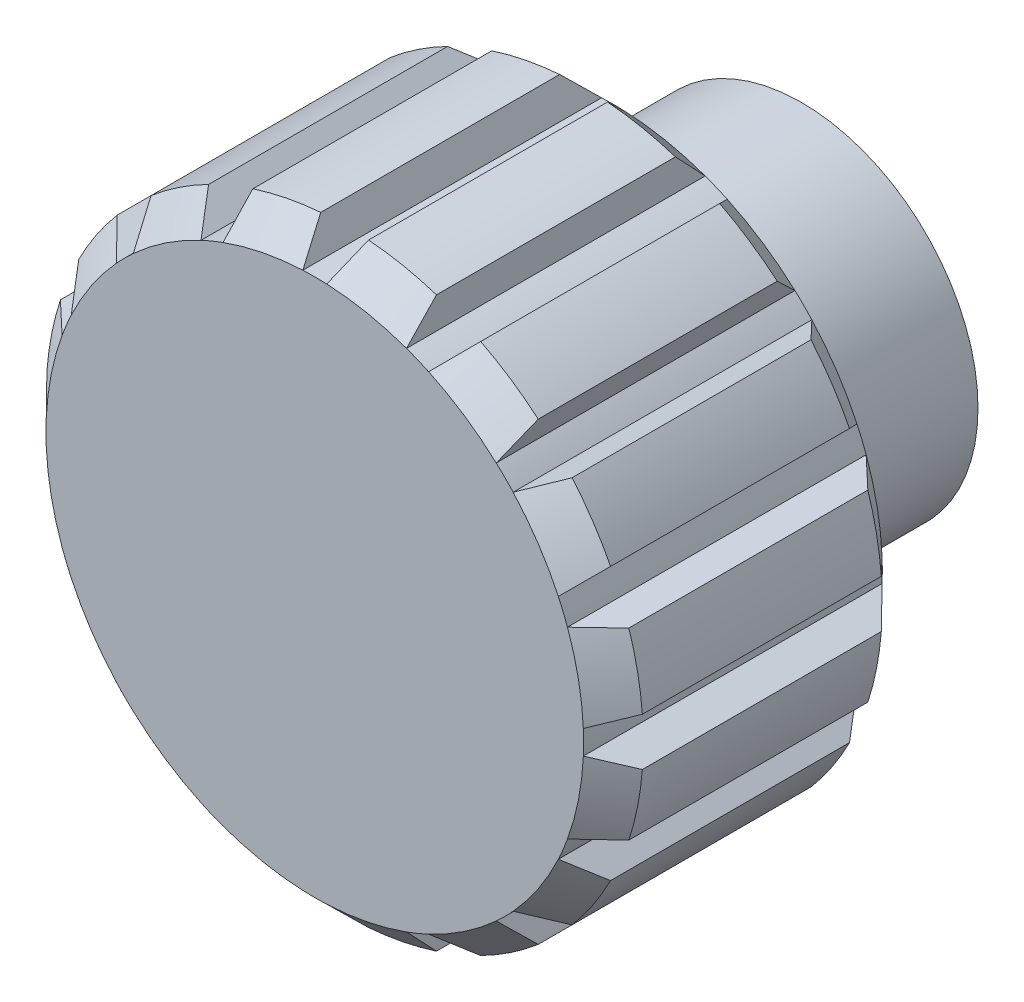
SolidWorks part; units mm, degrees
ref_plane "Front Plane" through (0, 0, 0) normal (0, 0, 1) x (1, 0, 0)
ref_plane "Top Plane" through (0, 0, 0) normal (0, 1, 0) x (1, 0, 0)
ref_plane "Right Plane" through (0, 0, 0) normal (1, 0, 0) x (0, 0, -1)
sketch "Sketch1" plane through (0, 0, 0) normal (0, 0, 1) x (1, 0, 0)
  circle A0 centre (0, 0) radius 3.5
  circle A1 centre (0, 0) radius 7.5
  dimension "D1" = 7
  dimension "D2" = 15
extrude "Boss-Extrude1" add sketch "Sketch1" along normal blind 8
sketch "Sketch2" plane through (0, 0, 8) normal (0, 0, 1) x (1, 0, 0)
  circle A0 centre (0, 0) radius 12.7
  dimension "D1" = 25.4
extrude "Boss-Extrude2" add sketch "Sketch2" along normal blind 12.7
chamfer "Chamfer1" distance 1.27 angle 45 2 edges at (12.7, 0, 20.7) (12.7, 0, 8)
sketch "Sketch3" plane through (0, 0, 20.7) normal (0, 0, 1) x (1, 0, 0)
  line L0 (0, 13.8231) -> (0, 0) construction
  line L1 (-1.4946, 13.8231) -> (-0.508, 11.4187)
  line L2 (1.4946, 13.8231) -> (0.508, 11.4187)
  line L3 (-1.8993, 13.8231) -> (1.9378, 13.8231) construction
  line L4 (-1.4946, 13.8231) -> (1.4946, 13.8231)
  line L5 (3.9091, 13.3428) -> (6.6707, 12.1989)
  line L6 (6.6707, 12.1989) -> (4.8391, 10.3551)
  line L7 (3.9091, 13.3428) -> (3.9004, 10.7439)
  line L8 (8.7176, 10.8312) -> (10.8312, 8.7176)
  line L9 (10.8312, 8.7176) -> (8.4335, 7.715)
  line L10 (8.7176, 10.8312) -> (7.715, 8.4335)
  line L11 (12.1989, 6.6707) -> (13.3428, 3.9091)
  line L12 (13.3428, 3.9091) -> (10.7439, 3.9004)
  line L13 (12.1989, 6.6707) -> (10.3551, 4.8391)
  line L14 (13.8231, 1.4946) -> (13.8231, -1.4946)
  line L15 (13.8231, -1.4946) -> (11.4187, -0.508)
  line L16 (13.8231, 1.4946) -> (11.4187, 0.508)
  line L17 (13.3428, -3.9091) -> (12.1989, -6.6707)
  line L18 (12.1989, -6.6707) -> (10.3551, -4.8391)
  line L19 (13.3428, -3.9091) -> (10.7439, -3.9004)
  line L20 (10.8312, -8.7176) -> (8.7176, -10.8312)
  line L21 (8.7176, -10.8312) -> (7.715, -8.4335)
  line L22 (10.8312, -8.7176) -> (8.4335, -7.715)
  line L23 (6.6707, -12.1989) -> (3.9091, -13.3428)
  line L24 (3.9091, -13.3428) -> (3.9004, -10.7439)
  line L25 (6.6707, -12.1989) -> (4.8391, -10.3551)
  line L26 (1.4946, -13.8231) -> (-1.4946, -13.8231)
  line L27 (-1.4946, -13.8231) -> (-0.508, -11.4187)
  line L28 (1.4946, -13.8231) -> (0.508, -11.4187)
  line L29 (-3.9091, -13.3428) -> (-6.6707, -12.1989)
  line L30 (-6.6707, -12.1989) -> (-4.8391, -10.3551)
  line L31 (-3.9091, -13.3428) -> (-3.9004, -10.7439)
  line L32 (-8.7176, -10.8312) -> (-10.8312, -8.7176)
  line L33 (-10.8312, -8.7176) -> (-8.4335, -7.715)
  line L34 (-8.7176, -10.8312) -> (-7.715, -8.4335)
  line L35 (-12.1989, -6.6707) -> (-13.3428, -3.9091)
  line L36 (-13.3428, -3.9091) -> (-10.7439, -3.9004)
  line L37 (-12.1989, -6.6707) -> (-10.3551, -4.8391)
  line L38 (-13.8231, -1.4946) -> (-13.8231, 1.4946)
  line L39 (-13.8231, 1.4946) -> (-11.4187, 0.508)
  line L40 (-13.8231, -1.4946) -> (-11.4187, -0.508)
  line L41 (-13.3428, 3.9091) -> (-12.1989, 6.6707)
  line L42 (-12.1989, 6.6707) -> (-10.3551, 4.8391)
  line L43 (-13.3428, 3.9091) -> (-10.7439, 3.9004)
  line L44 (-10.8312, 8.7176) -> (-8.7176, 10.8312)
  line L45 (-8.7176, 10.8312) -> (-7.715, 8.4335)
  line L46 (-10.8312, 8.7176) -> (-8.4335, 7.715)
  line L47 (-6.6707, 12.1989) -> (-3.9091, 13.3428)
  line L48 (-3.9091, 13.3428) -> (-3.9004, 10.7439)
  line L49 (-6.6707, 12.1989) -> (-4.8391, 10.3551)
  circle A1 centre (0, 0) radius 11.43 construction
  arc A2 (0.508, 11.4187) -> (-0.508, 11.4187) centre (0, 0) ccw
  arc A3 (4.8391, 10.3551) -> (3.9004, 10.7439) centre (0, 0) ccw
  arc A4 (8.4335, 7.715) -> (7.715, 8.4335) centre (0, 0) ccw
  arc A5 (10.7439, 3.9004) -> (10.3551, 4.8391) centre (0, 0) ccw
  arc A6 (11.4187, -0.508) -> (11.4187, 0.508) centre (0, 0) ccw
  arc A7 (10.3551, -4.8391) -> (10.7439, -3.9004) centre (0, 0) ccw
  arc A8 (7.715, -8.4335) -> (8.4335, -7.715) centre (0, 0) ccw
  arc A9 (3.9004, -10.7439) -> (4.8391, -10.3551) centre (0, 0) ccw
  arc A10 (-0.508, -11.4187) -> (0.508, -11.4187) centre (0, 0) ccw
  arc A11 (-4.8391, -10.3551) -> (-3.9004, -10.7439) centre (0, 0) ccw
  arc A12 (-8.4335, -7.715) -> (-7.715, -8.4335) centre (0, 0) ccw
  arc A13 (-10.7439, -3.9004) -> (-10.3551, -4.8391) centre (0, 0) ccw
  arc A14 (-11.4187, 0.508) -> (-11.4187, -0.508) centre (0, 0) ccw
  arc A15 (-10.3551, 4.8391) -> (-10.7439, 3.9004) centre (0, 0) ccw
  arc A16 (-7.715, 8.4335) -> (-8.4335, 7.715) centre (0, 0) ccw
  arc A17 (-3.9004, 10.7439) -> (-4.8391, 10.3551) centre (0, 0) ccw
  point P72 (0, 0)
  dimension "D1" = 16
  dimension "D2" = 0.508
extrude "Cut-Extrude2" cut sketch "Sketch3" against normal blind 12.7
